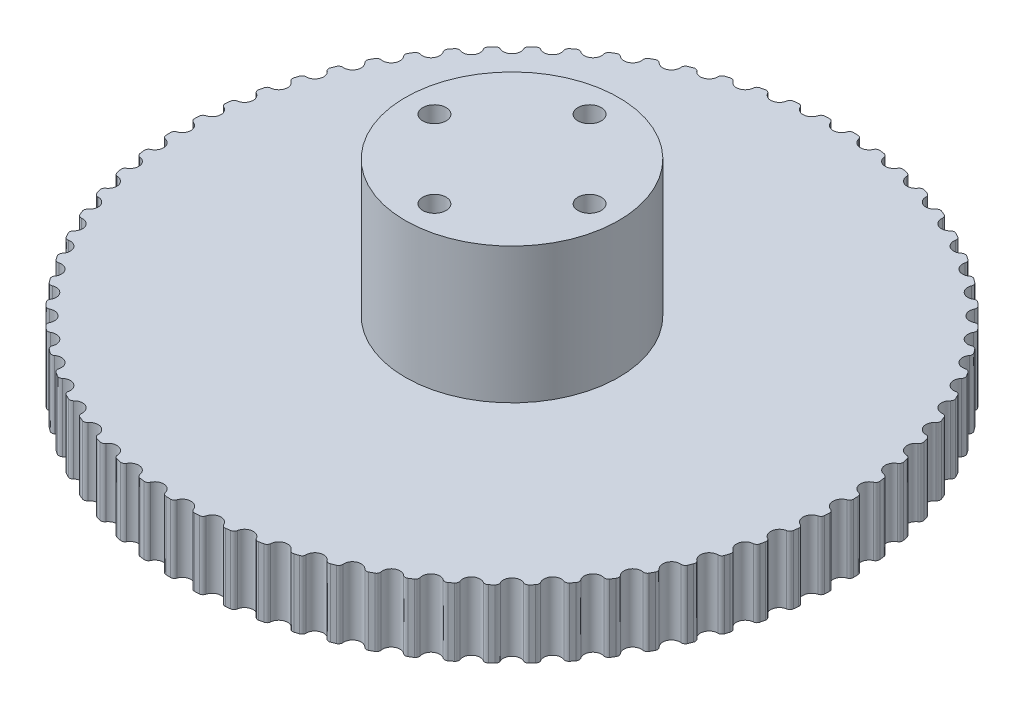
SolidWorks part; units mm, degrees
ref_plane "Front Plane" through (0, 0, 0) normal (0, 0, 1) x (1, 0, 0)
ref_plane "Top Plane" through (0, 0, 0) normal (0, 1, 0) x (1, 0, 0)
ref_plane "Right Plane" through (0, 0, 0) normal (1, 0, 0) x (0, 0, -1)
sketch "Sketch1" plane through (0, 0, 0) normal (0, 1, 0) x (1, 0, 0)
  circle A0 centre (0, 0) radius 34
  dimension "D1" = 68
extrude "Boss-Extrude1" add sketch "Sketch1" along normal blind 7
sketch "Sketch2" plane through (0, 7, 0) normal (0, 1, 0) x (1, 0, 0)
  circle A0 centre (0, 0) radius 11
  dimension "D1" = 22
extrude "Boss-Extrude2" add sketch "Sketch2" along normal blind 14
sketch "Sketch4" plane through (0, 0, 0) normal (0, -1, 0) x (1, 0, 0)
  line L0 (-8, 0) -> (0, 0) construction
  circle A0 centre (-8, 0) radius 2.25
  dimension "D1" = 4.5
  dimension "D2" = 8
extrude "Cut-Extrude1" cut sketch "Sketch4" against normal offset from surface (18 mm away) 3 up to face at (0, 21, 11)
hole_wizard "CSK for M2 Countersunk Flat Head Screw1" positions "3DSketch1" profile "Sketch5" countersink size "M2" standard "ISO" end condition through all
sketch3d "3DSketch1"
  line L0 (-8, 18, 0) -> (-8, 0, 0) construction
  point P0 (-8, 18, 0)
sketch "Sketch5" plane through (-8, 18, 0) normal (1, 0, 0) x (0, 0, -1)
  line L0 (0, 0) -> (0, 3)
  line L1 (0, 3) -> (1.2, 3)
  line L2 (1.2, 3) -> (1.2, 1)
  line L3 (1.2, 1) -> (2.2, 0)
  line L5 (2.2, 0) -> (0, 0)
  line L6 (-1.2, 1) -> (-2.2, 0) construction
  line L11 (0, -6.35) -> (0, 107.95) construction
  dimension "Thru Hole Dia." = 2.4
  dimension "Thru Hole Depth" = 3
  dimension "Near C'Sink Dia." = 4.4
  dimension "Near C'Sink Angle" = 90
pattern_circular "CirPattern1" count 4 over 360 about axis through (0, 7, 0) along (0, -1, 0) of "CSK for M2 Countersunk Flat Head Screw1", "Cut-Extrude1"
sketch "Sketch6" plane through (0, 7, 0) normal (0, 1, 0) x (1, 0, 0)
  arc A0 (0.8512, 33.7075) -> (-0.8512, 33.7075) centre (0, 34) cw
  circle A1 centre (0, 0) radius 34 construction
  arc A5 (1.2441, 33.9772) -> (0.8512, 33.7075) centre (1.2295, 33.5775) ccw
  arc A6 (-1.2441, 33.9772) -> (-0.8512, 33.7075) centre (-1.2295, 33.5775) cw
  arc A7 (1.2441, 33.9772) -> (-1.2441, 33.9772) centre (0, 0) ccw
  point P1 (0, 0)
  dimension "D2" = 0.4
  dimension "D3" = 0.4
extrude "Cut-Extrude2" cut sketch "Sketch6" against normal through all
pattern_circular "CirPattern2" count 72 over 360 about axis through (0, 21, 0) along (0, -1, 0) of "Cut-Extrude2" reverse direction yes
